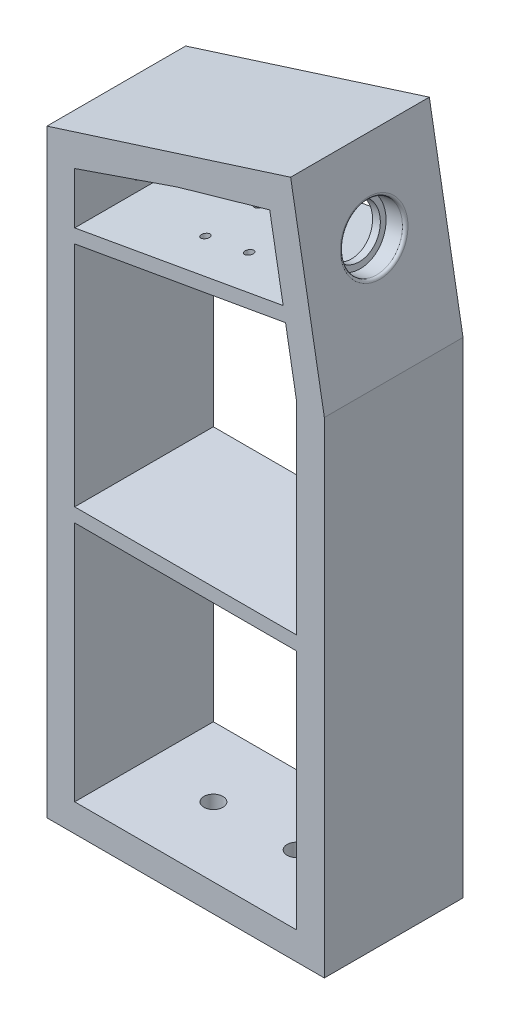
SolidWorks part; units mm, degrees
ref_plane "Front Plane" through (0, 0, 0) normal (0, 0, 1) x (1, 0, 0)
ref_plane "Top Plane" through (0, 0, 0) normal (0, 1, 0) x (1, 0, 0)
ref_plane "Right Plane" through (0, 0, 0) normal (1, 0, 0) x (0, 0, -1)
sketch "Sketch2" plane through (0, 0, 0) normal (0, 0, 1) x (1, 0, 0)
  line L6 (-40.869, 215.9795) -> (-40.869, 0)
  line L8 (-40.869, 0) -> (59.131, 0)
  line L10 (-40.869, 215.9795) -> (59.131, 0) construction
  line L11 (-40.869, 0) -> (59.131, 215.9795) construction
  line L12 (59.131, 0) -> (59.131, 175)
  line L13 (59.131, 175) -> (46.9756, 243.9365)
  line L14 (59.131, 175) -> (59.131, 266.0824) construction
  line L15 (46.9756, 243.9365) -> (-40.869, 215.9795)
  line L16 (-40.869, 107.9897) -> (-30.869, 107.9897) construction
  line L17 (3.0533, 229.958) -> (6.086, 220.4289) construction
  line L18 (59.131, 87.5) -> (49.131, 87.5) construction
  line L19 (0, 0) -> (0, 10) construction
  line L20 (0, 10) -> (49.131, 10)
  line L21 (49.131, 10) -> (49.131, 87.5)
  line L22 (49.131, 87.5) -> (49.131, 175)
  line L23 (53.0533, 209.4683) -> (43.2052, 207.7318) construction
  line L24 (49.131, 175) -> (39.4404, 229.958)
  line L25 (39.4404, 229.958) -> (6.086, 220.4289)
  line L26 (6.086, 220.4289) -> (-30.869, 207.7318)
  line L27 (-30.869, 207.7318) -> (-30.869, 107.9897)
  line L28 (-30.869, 107.9897) -> (-30.869, 10)
  line L29 (-30.869, 10) -> (0, 10)
  point P1 (9.131, 107.9897)
  dimension "D2" = 100
  dimension "D3" = 10
  dimension "D4" = 6.086
  dimension "D5" = 9.131
  dimension "D6" = 39.4404
  dimension "D7" = 46.9756
extrude "Boss-Extrude1" add sketch "Sketch2" along normal blind 50
sketch "Sketch4" plane through (87.2747, 15.3889, 0) normal (0.9848, 0.1736, 0) x (0, 0, -1)
  line L0 (-25, 162.0734) -> (-25, 202.6904) construction
  line L1 (-50, 162.0734) -> (0, 162.0734) construction
  line L2 (-50, 232.0734) -> (0, 232.0734) construction
  circle A0 centre (-25, 202.6904) radius 11.025
  dimension "D1" = 22.05
  dimension "D2" = 29.383
extrude "Cut-Extrude1" cut sketch "Sketch4" against normal blind 7
sketch "Sketch5" plane through (80.3811, 14.1734, 0) normal (0.9848, 0.1736, 0) x (0, 0, -1)
  line L0 (-25, 213.7154) -> (-25, 191.6654) construction
  circle A0 centre (-25, 202.6904) radius 11.025 construction
  circle A1 centre (-25, 202.6904) radius 11.025 construction
  circle A2 centre (-25, 202.6904) radius 9
  dimension "D1" = 18
extrude "Cut-Extrude2" cut sketch "Sketch5" against normal blind 7
sketch "Sketch7" plane through (0, 0, 50) normal (0, 0, 1) x (1, 0, 0)
  line L0 (39.4404, 229.958) -> (44.2785, 202.5195) construction
  line L1 (49.131, 175) -> (39.4404, 229.958) construction
  line L2 (-30.869, 207.7318) -> (-30.869, 189.1918) construction
  line L3 (-30.869, 207.7318) -> (-30.869, 10) construction
  line L5 (44.2785, 202.5195) -> (45.1468, 197.5954)
  line L6 (45.1468, 197.5954) -> (-30.869, 184.1918)
  line L7 (-30.869, 184.1918) -> (-30.869, 189.1918)
  line L9 (-40.869, 215.9795) -> (-40.869, 0) construction
  line L10 (44.2785, 202.5195) -> (-30.869, 189.1918)
  dimension "D1" = 85.1476
  dimension "D2" = 86.0158
extrude "Boss-Extrude2" add sketch "Sketch7" against normal blind 50
sketch "Sketch8" plane through (-40.869, 0, 0) normal (-1, 0, 0) x (0, 0, 1)
  line L1 (50, 215.9795) -> (50, 0) construction
  line L2 (0, 202.5195) -> (0, 197.1539) construction
  line L3 (0, 215.9795) -> (0, 0) construction
  line L4 (0, 197.1539) -> (50, 197.1539) construction
  circle A0 centre (25, 197.1539) radius 5
  dimension "D1" = 10
extrude "Cut-Extrude3" cut sketch "Sketch8" against normal blind 10
sketch "Sketch9" plane through (-32.4295, 183.9166, 0) normal (0.1736, -0.9848, 0) x (0.9848, 0.1736, 0)
  line L0 (78.773, 25) -> (54.1984, 25) construction
  line L3 (78.773, 0) -> (78.773, 50) construction
  line L4 (42.6945, 15.833) -> (42.6945, 33.6873) construction
  line L5 (42.6945, 25) -> (50.6945, 25)
  line L6 (50.6945, 25) -> (50.6945, 34.6)
  line L7 (50.6945, 25) -> (50.6945, 15.4) construction
  line L9 (1.5845, 0) -> (1.5845, 50) construction
  circle A0 centre (50.6945, 15.4) radius 1.485
  circle A1 centre (50.6945, 34.6) radius 1.485
  circle A2 centre (34.6945, 34.6) radius 1.485
  circle A3 centre (34.6945, 15.4) radius 1.485
  dimension "D1" = 33.11
  dimension "D2" = 2.97
  dimension "D3" = 41.11
  dimension "D4" = 15.4
extrude "Cut-Extrude4" cut sketch "Sketch9" against normal up to next contours A2 | A0 | A1 | A3 region at (17.4949, 192.7197, 15.4) region at (18.4997, 192.8968, 33.5796) region at (1.738, 189.9413, 34.6)
sketch "Sketch10" plane through (0, 10, 0) normal (0, 1, 0) x (1, 0, 0)
  line L0 (49.131, -25) -> (24.131, -25) construction
  line L1 (-30.869, -50) -> (-30.869, 0) construction
  line L3 (-30.869, -25) -> (-5.8513, -25) construction
  line L4 (49.131, -50) -> (49.131, 0) construction
  circle A0 centre (-5.8513, -25) radius 3.425
  circle A1 centre (24.131, -25) radius 3.425
  dimension "D1" = 6.85
  dimension "D2" = 6.85
  dimension "D3" = 25.0177
  dimension "D4" = 55
extrude "Cut-Extrude5" cut sketch "Sketch10" against normal blind 10
sketch "Sketch11" plane through (0, 0, 50) normal (0, 0, 1) x (1, 0, 0)
  line L0 (-30.869, 97.0959) -> (49.131, 97.0959)
  line L1 (-30.869, 184.1918) -> (-30.869, 10) construction
  line L2 (49.131, 10) -> (49.131, 175) construction
  line L3 (49.131, 97.0959) -> (49.131, 102.0959)
  line L4 (49.131, 102.0959) -> (-30.869, 102.0959)
  line L5 (-30.869, 102.0959) -> (-30.869, 97.0959)
  dimension "D1" = 5
extrude "Boss-Extrude3" add sketch "Sketch11" against normal blind 50
fillet "Fillet1" radius 1 1 edges at (50.1634, 225.8574, 25) type face fillet first side face at (43.2698, 224.6419, 25) second side face at (50.1634, 225.8574, 25)
